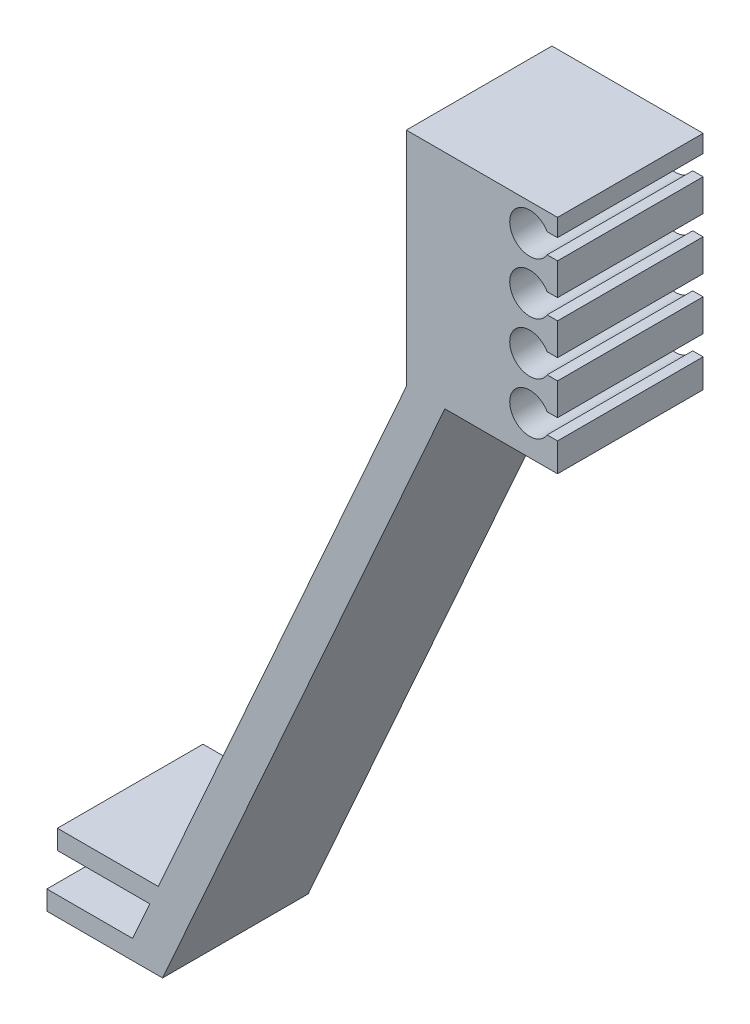
SolidWorks part; units mm, degrees
ref_plane "Front Plane" through (0, 0, 0) normal (0, 0, 1) x (1, 0, 0)
ref_plane "Top Plane" through (0, 0, 0) normal (0, 1, 0) x (1, 0, 0)
ref_plane "Right Plane" through (0, 0, 0) normal (1, 0, 0) x (0, 0, -1)
sketch "Sketch1" plane through (0, 0, 0) normal (0, 0, 1) x (1, 0, 0)
  line L2 (-159.7982, 9.1286) -> (-172.2482, 9.1286)
  line L3 (-172.2482, 9.1286) -> (-172.2482, -9.1594)
  line L7 (-169.2482, -22.8519) -> (-169.2482, 6.1286) construction
  line L13 (-142.8048, 5.144) -> (-142.8048, -5.1748) construction
  line L23 (-159.7982, 6.1286) -> (-159.7982, 9.1286)
  line L28 (-164.5232, 5.1786) -> (-144.5007, 5.1786) construction
  line L30 (-169.2482, 6.1286) -> (-169.2482, 5.1286)
  line L34 (-169.2482, 5.1286) -> (-169.2482, -5.1594)
  line L35 (-172.2482, -0.0154) -> (-169.2482, -0.0154) construction
  line L36 (-169.2482, -6.1594) -> (-169.2482, -5.1594)
  line L37 (-159.7982, -6.1594) -> (-159.7982, -9.1594)
  line L38 (-159.7982, -9.1594) -> (-172.2482, -9.1594)
  arc A5 (-169.2482, 6.1286) -> (-159.7982, 6.1286) centre (-164.5232, 17.404) ccw
  arc A6 (-169.2482, -6.1594) -> (-159.7982, -6.1594) centre (-164.5232, -17.4347) cw
  point P30 (-142.8048, -0.0154)
  dimension "D6" = 12.2253
  dimension "D4" = 3
  dimension "D3" = 3
  dimension "D2" = 1
  dimension "D1" = 18.288
  dimension "D5" = 12.45
extrude "MainBody" add sketch "Sketch1" along normal mid plane 11.9888
sketch "Sketch3" plane through (0, -9.1594, 0) normal (0, -1, 0) x (1, 0, 0)
  line L0 (-159.7982, -5.9944) -> (-162.3382, -6.9944)
  line L1 (-162.3382, -6.9944) -> (-162.3382, -5.9944)
  line L2 (-172.2482, -5.9944) -> (-159.7982, -5.9944) construction
  line L3 (-162.3382, -5.9944) -> (-159.7982, -5.9944)
  line L5 (23.1247, 0) -> (-23.1247, 0) construction
  line L6 (-162.3382, 5.9944) -> (-159.7982, 5.9944)
  line L7 (-162.3382, 6.9944) -> (-162.3382, 5.9944)
  line L8 (-159.7982, 5.9944) -> (-162.3382, 6.9944)
  dimension "D1" = 2.54
  dimension "D2" = 1
extrude "Hook" [suppressed] add sketch "Sketch3" against normal up to vertex up to point (-159.7982, -6.1594, -5.9944)
fillet "Fillet2" [suppressed] radius 1
sketch "Sketch5" [suppressed] plane through (-172.2482, 0, 0) normal (-1, 0, 0) x (0, 0, 1)
  line L1 (-6, 9.1594) -> (6, 9.1594)
  line L2 (-6, 9.1594) -> (-6, -9.1594)
  line L3 (-6, -9.1594) -> (6, -9.1594)
  line L4 (6, 9.1594) -> (6, -9.1594)
extrude "Boss-Extrude1" [suppressed] add sketch "Sketch5" along normal blind 15
sketch "Sketch6" [suppressed] plane through (0, 9.1594, 0) normal (0, 1, 0) x (1, 0, 0)
  line L0 (-187.2482, -6) -> (-187.2482, 6) construction
  circle A0 centre (-182.2482, 0) radius 3.302
  dimension "D1" = 6.604
  dimension "D2" = 5
extrude "Cut-Extrude2" [suppressed] cut sketch "Sketch6" against normal through all
sketch "Sketch7" plane through (-172.2482, 0, 0) normal (-1, 0, 0) x (0, 0, 1)
  circle A0 centre (0, 0) radius 38.1
  dimension "D1" = 76.2
extrude "Boss-Extrude2" [suppressed] add sketch "Sketch7" along normal blind 5
fillet "Fillet3" [suppressed] radius 1
sketch "Sketch8" plane through (0, 0, 5.9944) normal (0, 0, 1) x (1, 0, 0)
  line L6 (-172.2482, -0.635) -> (-173.4343, -0.635)
  line L8 (-172.2482, 0.635) -> (-173.4343, 0.635)
  line L10 (-172.2482, 0.635) -> (-173.4343, 0.635)
  line L11 (-172.2482, 0.635) -> (-172.2482, -0.635)
  line L12 (-159.7982, -9.1594) -> (-159.7982, -6.1594)
  line L14 (-169.2482, -6.1594) -> (-169.2482, 6.1286)
  line L15 (-159.7982, 6.1286) -> (-159.7982, 9.1286)
  line L16 (-159.7982, 9.1286) -> (-172.2482, 9.1286)
  line L17 (-172.2482, 9.1286) -> (-172.2482, -9.1594)
  line L18 (-172.2482, -9.1594) -> (-159.7982, -9.1594)
  line L21 (-169.2482, -6.1594) -> (-169.2482, 6.1286)
  line L22 (-159.7982, 6.1286) -> (-159.7982, 9.1286)
  line L23 (-159.7982, 9.1286) -> (-172.2482, 9.1286)
  line L24 (-172.2482, 9.1286) -> (-172.2482, -9.1594)
  line L25 (-172.2482, -9.1594) -> (-159.7982, -9.1594)
  line L26 (-172.2482, -0.635) -> (-173.4343, -0.635)
  line L33 (-159.7982, -9.1594) -> (-159.7982, -6.1594)
  arc A0 (-173.4343, 0.635) -> (-173.4343, -0.635) centre (-174.5342, 0) ccw
  arc A4 (-159.7982, -6.1594) -> (-169.2482, -6.1594) centre (-164.5232, -17.4347) ccw
  arc A7 (-169.2482, 6.1286) -> (-159.7982, 6.1286) centre (-164.5232, 17.404) ccw
  arc A8 (-159.7982, -6.1594) -> (-169.2482, -6.1594) centre (-164.5232, -17.4347) ccw
  arc A11 (-169.2482, 6.1286) -> (-159.7982, 6.1286) centre (-164.5232, 17.404) ccw
  point P6 (-172.2482, -0.0154)
  dimension "D2" = 1.27
  dimension "D1" = 0
  dimension "D3" = 2.286
extrude "Slot" [suppressed] add sketch "Sketch8" against normal up to surface (12 mm away) up to face at (-165.2732, -0.0154, -5.9944)
sketch "Sketch10" plane through (0, 0, -5.9944) normal (0, 0, -1) x (-1, 0, 0)
  line L0 (166.0232, -9.1594) -> (172.2482, -9.1594)
  line L3 (172.2482, -9.1594) -> (166.0232, -9.1594)
  line L5 (172.2482, -9.1594) -> (187.9767, -44.4861)
  line L6 (195.4932, -61.3685) -> (192.3182, -61.3685)
  line L7 (159.7982, -6.1594) -> (159.7982, -9.1594)
  line L9 (159.7982, -9.1594) -> (172.2482, -9.1594)
  line L10 (172.2482, -9.1594) -> (172.2482, 9.1286)
  line L11 (172.2482, 9.1286) -> (159.7982, 9.1286)
  line L12 (159.7982, 9.1286) -> (159.7982, 6.1286)
  line L13 (169.2482, 6.1286) -> (169.2482, -6.1594)
  line L16 (159.7982, -9.1594) -> (172.2482, -9.1594)
  line L17 (172.2482, -9.1594) -> (172.2482, 9.1286)
  line L18 (172.2482, 9.1286) -> (159.7982, 9.1286)
  line L19 (159.7982, 9.1286) -> (159.7982, 6.1286)
  line L20 (169.2482, 6.1286) -> (169.2482, -6.1594)
  line L21 (195.4932, -61.3685) -> (201.8432, -61.3685)
  line L22 (201.8432, -61.3685) -> (201.8432, -59.781)
  line L24 (192.666, -55.0185) -> (200.9772, -55.0185)
  line L25 (169.0732, -9.1594) -> (192.3182, -61.3685)
  line L28 (201.8432, -59.781) -> (194.7864, -59.781)
  line L31 (193.3728, -56.606) -> (200.9772, -56.606)
  line L42 (200.9772, -55.0185) -> (200.9772, -56.606)
  line L43 (187.9767, -44.4861) -> (195.4932, -61.3685)
  line L49 (159.7982, -6.1594) -> (159.7982, -9.1594)
  arc A4 (169.2482, -6.1594) -> (159.7982, -6.1594) centre (164.5232, -17.4347) ccw
  arc A5 (159.7982, 6.1286) -> (169.2482, 6.1286) centre (164.5232, 17.404) ccw
  arc A8 (169.2482, -6.1594) -> (159.7982, -6.1594) centre (164.5232, -17.4347) ccw
  arc A9 (159.7982, 6.1286) -> (169.2482, 6.1286) centre (164.5232, 17.404) ccw
  dimension "D5" = 6.35
  dimension "D7" = 3.175
  dimension "D8" = 3.175
  dimension "D2" = 57.15
  dimension "D10" = 1.5875
  dimension "D13" = 114
  dimension "D14" = 114
  dimension "D3" = 1.5875
  dimension "D4" = 3.175
extrude "Boss-Extrude3" add sketch "Sketch10" against normal up to surface (11.9888 mm away) contours L6 L5 | L28 L43 L21 L22 | L43 | L43 | L43 | L43 L31 region at (-182.2832, -35.2639, -5.9944) region at (-198.4884, -60.5608, -5.9944) region at (-196.9956, -55.8005, -5.9944) up to face at (-165.2732, -0.0154, 5.9944)
sketch "Sketch11" plane through (0, 0, -5.9944) normal (0, 0, -1) x (-1, 0, 0)
  line L0 (159.7982, -9.1594) -> (159.7982, 9.1286)
  line L11 (169.2482, 6.1286) -> (169.2482, -6.1594)
  line L12 (159.7982, -6.1594) -> (159.7982, -9.1594)
  line L13 (159.7982, -9.1594) -> (169.0732, -9.1594)
  line L14 (169.0732, -9.1594) -> (192.3182, -61.3685)
  line L15 (192.3182, -61.3685) -> (201.8432, -61.3685)
  line L16 (201.8432, -61.3685) -> (201.8432, -59.781)
  line L17 (201.8432, -59.781) -> (194.7864, -59.781)
  line L18 (194.7864, -59.781) -> (193.3728, -56.606)
  line L19 (172.2482, -9.1594) -> (172.2482, 9.1286)
  line L20 (172.2482, 9.1286) -> (159.7982, 9.1286)
  line L21 (159.7982, 9.1286) -> (159.7982, 6.1286)
  line L22 (169.2482, 6.1286) -> (169.2482, -6.1594)
  line L23 (159.7982, -6.1594) -> (159.7982, -9.1594)
  line L24 (159.7982, -9.1594) -> (169.0732, -9.1594)
  line L25 (169.0732, -9.1594) -> (192.3182, -61.3685)
  line L26 (192.3182, -61.3685) -> (201.8432, -61.3685)
  line L27 (201.8432, -61.3685) -> (201.8432, -59.781)
  line L28 (201.8432, -59.781) -> (194.7864, -59.781)
  line L29 (194.7864, -59.781) -> (193.3728, -56.606)
  line L30 (172.2482, -9.1594) -> (172.2482, 9.1286)
  line L31 (172.2482, 9.1286) -> (159.7982, 9.1286)
  line L32 (159.7982, 9.1286) -> (159.7982, 6.1286)
  line L37 (193.3728, -56.606) -> (200.9772, -56.606)
  line L38 (193.3728, -56.606) -> (200.9772, -56.606)
  line L39 (200.9772, -56.606) -> (200.9772, -55.0185)
  line L40 (200.9772, -56.606) -> (200.9772, -55.0185)
  line L41 (192.666, -55.0185) -> (172.2482, -9.1594)
  line L42 (192.666, -55.0185) -> (172.2482, -9.1594)
  line L44 (200.9772, -55.0185) -> (192.666, -55.0185)
  line L45 (200.9772, -55.0185) -> (192.666, -55.0185)
  arc A2 (159.7982, 6.1286) -> (169.2482, 6.1286) centre (164.5232, 17.404) ccw
  arc A3 (169.2482, -6.1594) -> (159.7982, -6.1594) centre (164.5232, -17.4347) ccw
  arc A4 (159.7982, 6.1286) -> (169.2482, 6.1286) centre (164.5232, 17.404) ccw
  arc A5 (169.2482, -6.1594) -> (159.7982, -6.1594) centre (164.5232, -17.4347) ccw
  dimension "D1" = 0
extrude "Boss-Extrude4" add sketch "Sketch11" against normal up to surface (11.9888 mm away) contours L0 region at (-164.5232, -0.0154, -5.9944) up to face at (-180.5907, -27.9312, 5.9944)
sketch "Sketch12" plane through (0, 0, -5.9944) normal (0, 0, -1) x (-1, 0, 0)
  line L0 (159.7982, -9.1594) -> (159.7982, -5.9844)
  line L1 (159.7982, -5.9844) -> (162.0842, -5.9844)
  line L3 (162.0842, -5.1589) -> (159.7982, -5.1589)
  line L4 (162.0842, -5.1589) -> (162.0842, -6.8099)
  line L5 (162.0842, -6.8099) -> (159.7982, -6.8099)
  line L6 (159.7982, -5.1589) -> (159.7982, -6.8099)
  line L7 (162.0842, -5.1589) -> (159.7982, -6.8099) construction
  line L8 (162.0842, -6.8099) -> (159.7982, -5.1589) construction
  line L9 (172.2482, 9.1286) -> (159.7982, 9.1286)
  line L10 (159.7982, 9.1286) -> (159.7982, -9.1594)
  line L11 (159.7982, -9.1594) -> (169.0732, -9.1594)
  line L12 (169.0732, -9.1594) -> (192.3182, -61.3685)
  line L13 (192.3182, -61.3685) -> (201.8432, -61.3685)
  line L14 (201.8432, -61.3685) -> (201.8432, -59.781)
  line L15 (201.8432, -59.781) -> (194.7864, -59.781)
  line L16 (194.7864, -59.781) -> (193.3728, -56.606)
  line L17 (172.2482, -9.1594) -> (172.2482, 9.1286)
  line L18 (172.2482, 9.1286) -> (159.7982, 9.1286)
  line L19 (159.7982, 9.1286) -> (159.7982, -9.1594)
  line L20 (159.7982, -9.1594) -> (169.0732, -9.1594)
  line L21 (169.0732, -9.1594) -> (192.3182, -61.3685)
  line L22 (192.3182, -61.3685) -> (201.8432, -61.3685)
  line L23 (201.8432, -61.3685) -> (201.8432, -59.781)
  line L24 (201.8432, -59.781) -> (194.7864, -59.781)
  line L25 (194.7864, -59.781) -> (193.3728, -56.606)
  line L26 (172.2482, -9.1594) -> (172.2482, 9.1286)
  line L38 (193.3728, -56.606) -> (200.9772, -56.606)
  line L39 (193.3728, -56.606) -> (200.9772, -56.606)
  line L40 (200.9772, -56.606) -> (200.9772, -55.0185)
  line L42 (192.666, -55.0185) -> (172.2482, -9.1594)
  line L43 (192.666, -55.0185) -> (172.2482, -9.1594)
  line L45 (200.9772, -56.606) -> (200.9772, -55.0185)
  line L46 (200.9772, -55.0185) -> (192.666, -55.0185)
  line L47 (200.9772, -55.0185) -> (192.666, -55.0185)
  circle A0 centre (162.0842, -5.9844) radius 1.651
  point P8 (160.9412, -5.9844)
  line M13 (159.7982, 9.1286) -> (159.7982, -9.1594)
  dimension "D4" = 3.302
  dimension "D2" = 3.175
  dimension "D3" = 2.286
  dimension "D5" = 1.651
extrude "Cut-Extrude3" cut sketch "Sketch12" against normal up to surface (11.9888 mm away) contours L5 A0 L3 L4 | L1 A0 L5 L4 | A0 L1 L5 M13 | L3 A0 L1 L4 | A0 L3 L1 M13 region at (-160.1545, -6.4183, -5.9944) region at (-160.1545, -5.5504, -5.9944) region at (-161.2931, -6.3876, -5.9944) region at (-162.4305, -5.9844, -5.9944) region at (-161.2931, -5.5811, -5.9944) up to face at (-185.5346, -36.5207, 5.9944)
pattern_linear "LPattern1" count 4 spacing 4.28 along (0, 1, 0) of "Cut-Extrude3"
sketch "Sketch15" [suppressed] plane through (0, 0, 5.9944) normal (0, 0, 1) x (1, 0, 0)
  line L1 (-172.2482, -9.1594) -> (-179.8682, -9.1594)
  line L2 (-172.2482, -9.1594) -> (-172.2482, 47.9906)
  line L3 (-172.2482, 47.9906) -> (-179.8682, 47.9906)
  line L4 (-179.8682, -9.1594) -> (-179.8682, 47.9906)
  dimension "D1" = 7.62
  dimension "D2" = 69.85
extrude "Boss-Extrude6" [suppressed] add sketch "Sketch15" against normal up to surface (11.9888 mm away) up to face at (-171.9963, -16.131, -5.9944)
sketch "Sketch16" [suppressed] plane through (0, 0, 5.9944) normal (0, 0, 1) x (1, 0, 0)
  line L0 (-172.2482, 9.1286) -> (-172.2482, 47.9906) construction
  line L1 (-172.2482, 44.8156) -> (-174.5342, 44.8156)
  line L2 (-172.2482, 44.8156) -> (-172.2482, 43.1646)
  line L3 (-172.2482, 43.1646) -> (-174.5342, 43.1646)
  line L4 (-174.5342, 44.8156) -> (-174.5342, 43.1646)
  line L5 (-172.2482, 47.9906) -> (-179.8682, 47.9906) construction
  circle A0 centre (-174.5342, 43.9901) radius 1.5875
  line M12 (-172.2482, 9.1286) -> (-172.2482, 47.9906)
  dimension "D4" = 3.175
  dimension "D1" = 3.175
  dimension "D2" = 1.651
  dimension "D3" = 2.286
extrude "Cut-Extrude6" [suppressed] cut sketch "Sketch16" against normal up to surface (11.9888 mm away) contours A0 L3 L1 M12 | L3 A0 L1 L4 | L1 A0 L3 L4 up to face at (-171.9963, -16.131, -5.9944)
pattern_linear "LPattern3" [suppressed] count 9 spacing 5.08 of bodies 124
fillet "Fillet5" [suppressed] radius 2.54
sketch "Sketch17" [suppressed] plane through (0, 9.1286, 0) normal (0, 1, 0) x (1, 0, 0)
  line L1 (-164.7532, 6.096) -> (-167.2932, 6.096)
  line L2 (-164.7532, 6.096) -> (-164.7532, 3.556)
  line L3 (-164.7532, 3.556) -> (-167.2932, 3.556)
  line L4 (-159.7982, 6.096) -> (-172.2482, 6.096)
  line L5 (-172.2482, 6.096) -> (-172.2482, -6.096)
  line L6 (-172.2482, -6.096) -> (-159.7982, -6.096)
  line L7 (-159.7982, -6.096) -> (-159.7982, 6.096)
  line L8 (-159.7982, 6.096) -> (-172.2482, 6.096)
  line L9 (-172.2482, 6.096) -> (-172.2482, -6.096)
  line L10 (-172.2482, -6.096) -> (-159.7982, -6.096)
  line L11 (-159.7982, -6.096) -> (-159.7982, 6.096)
  line L12 (-167.2932, 6.096) -> (-167.2932, 3.556)
  point P8 (-166.0232, 6.096)
  point P9 (-166.0232, 6.096)
  dimension "D2" = 2.54
  dimension "D3" = 2.54
  dimension "D1" = 0
extrude "Boss-Extrude7" [suppressed] add sketch "Sketch17" along normal blind 6.35
pattern_linear "LPattern5" [suppressed] count 9 spacing 24.638 of bodies 126
sketch "Sketch21" [suppressed] plane through (0, 9.1286, 0) normal (0, 1, 0) x (1, 0, 0)
  line L1 (-167.2932, 5.9944) -> (-164.7532, 5.9944)
  line L2 (-167.2932, 5.9944) -> (-167.2932, 3.4544)
  line L3 (-167.2932, 3.4544) -> (-164.7532, 3.4544)
  line L4 (-159.7982, 5.9944) -> (-172.2482, 5.9944)
  line L5 (-172.2482, 5.9944) -> (-172.2482, -5.9944)
  line L6 (-172.2482, -5.9944) -> (-159.7982, -5.9944)
  line L7 (-159.7982, -5.9944) -> (-159.7982, 5.9944)
  line L8 (-159.7982, 5.9944) -> (-172.2482, 5.9944)
  line L9 (-172.2482, 5.9944) -> (-172.2482, -5.9944)
  line L10 (-172.2482, -5.9944) -> (-159.7982, -5.9944)
  line L11 (-159.7982, -5.9944) -> (-159.7982, 5.9944)
  line L12 (-164.7532, 5.9944) -> (-164.7532, 3.4544)
  point P8 (-166.0232, 5.9944)
  point P9 (-166.0232, 5.9944)
  dimension "D2" = 2.54
  dimension "D3" = 2.54
  dimension "D1" = 0
extrude "Boss-Extrude10" [suppressed] add sketch "Sketch21" along normal blind 6.35
sketch "Sketch22" [suppressed] plane through (-172.2482, 0, 0) normal (-1, 0, 0) x (0, 0, 1)
  line L1 (-5.9944, -1.2854) -> (-3.4544, -1.2854)
  line L2 (-5.9944, -1.2854) -> (-5.9944, 1.2546)
  line L3 (-5.9944, 1.2546) -> (-3.4544, 1.2546)
  line L4 (-5.9944, 9.1286) -> (-5.9944, -9.1594)
  line L5 (-5.9944, -9.1594) -> (5.9944, -9.1594)
  line L6 (5.9944, -9.1594) -> (5.9944, 9.1286)
  line L7 (5.9944, 9.1286) -> (-5.9944, 9.1286)
  line L8 (-5.9944, 9.1286) -> (-5.9944, -9.1594)
  line L9 (-5.9944, -9.1594) -> (5.9944, -9.1594)
  line L10 (5.9944, -9.1594) -> (5.9944, 9.1286)
  line L11 (5.9944, 9.1286) -> (-5.9944, 9.1286)
  line L12 (-3.4544, -1.2854) -> (-3.4544, 1.2546)
  point P8 (-5.9944, -0.0154)
  point P9 (-5.9944, -0.0154)
  dimension "D2" = 2.54
  dimension "D3" = 2.54
  dimension "D1" = 0
extrude "Boss-Extrude11" [suppressed] add sketch "Sketch22" along normal blind 6.35
pattern_linear "LPattern6" [suppressed] count 8 spacing 24.638 of bodies 164 160
sketch "Sketch20" [suppressed] plane through (-172.2482, 0, 0) normal (-1, 0, 0) x (0, 0, 1)
  line L1 (-6.096, -1.2854) -> (-3.556, -1.2854)
  line L2 (-6.096, -1.2854) -> (-6.096, 1.2546)
  line L3 (-6.096, 1.2546) -> (-3.556, 1.2546)
  line L4 (-6.096, 9.1286) -> (-6.096, -9.1594)
  line L5 (-6.096, -9.1594) -> (6.096, -9.1594)
  line L6 (6.096, -9.1594) -> (6.096, 9.1286)
  line L7 (6.096, 9.1286) -> (-6.096, 9.1286)
  line L8 (-6.096, 9.1286) -> (-6.096, -9.1594)
  line L9 (-6.096, -9.1594) -> (6.096, -9.1594)
  line L10 (6.096, -9.1594) -> (6.096, 9.1286)
  line L11 (6.096, 9.1286) -> (-6.096, 9.1286)
  line L12 (-3.556, -1.2854) -> (-3.556, 1.2546)
  point P8 (-6.096, -0.0154)
  point P9 (-6.096, -0.0154)
  dimension "D2" = 2.54
  dimension "D3" = 2.54
  dimension "D1" = 0
extrude "Boss-Extrude9" [suppressed] add sketch "Sketch20" along normal blind 6.35
sketch "Sketch23" [suppressed] plane through (0, 9.1286, 0) normal (0, 1, 0) x (1, 0, 0)
  line L0 (-167.2932, -5.9944) -> (-164.7532, -5.9944)
  line L4 (-159.7982, 5.9944) -> (-172.2482, 5.9944)
  line L5 (-172.2482, 5.9944) -> (-172.2482, -5.9944)
  line L6 (-172.2482, -5.9944) -> (-159.7982, -5.9944)
  line L7 (-159.7982, -5.9944) -> (-159.7982, 5.9944)
  line L8 (-159.7982, 5.9944) -> (-172.2482, 5.9944)
  line L9 (-172.2482, 5.9944) -> (-172.2482, -5.9944)
  line L10 (-172.2482, -5.9944) -> (-159.7982, -5.9944)
  line L11 (-159.7982, -5.9944) -> (-159.7982, 5.9944)
  line L13 (-164.7532, -5.9944) -> (-167.2932, -5.9944)
  line L14 (-164.7532, -5.9944) -> (-164.7532, -3.4544)
  line L15 (-164.7532, -3.4544) -> (-167.2932, -3.4544)
  line L16 (-167.2932, -5.9944) -> (-167.2932, -3.4544)
  point P8 (-166.0232, -5.9944)
  point P9 (-166.0232, -5.9944)
  dimension "D2" = 2.54
  dimension "D3" = 2.54
  dimension "D1" = 0
extrude "Boss-Extrude12" [suppressed] add sketch "Sketch23" along normal blind 6.35
sketch "Sketch27" [suppressed] plane through (-172.2482, 0, 0) normal (-1, 0, 0) x (0, 0, 1)
  line L1 (5.9944, -1.2854) -> (3.4544, -1.2854)
  line L2 (5.9944, -1.2854) -> (5.9944, 1.2546)
  line L3 (5.9944, 1.2546) -> (3.4544, 1.2546)
  line L4 (-5.9944, 9.1286) -> (-5.9944, -9.1594)
  line L5 (-5.9944, -9.1594) -> (5.9944, -9.1594)
  line L6 (5.9944, -9.1594) -> (5.9944, 9.1286)
  line L7 (5.9944, 9.1286) -> (-5.9944, 9.1286)
  line L8 (-5.9944, 9.1286) -> (-5.9944, -9.1594)
  line L9 (-5.9944, -9.1594) -> (5.9944, -9.1594)
  line L10 (5.9944, -9.1594) -> (5.9944, 9.1286)
  line L11 (5.9944, 9.1286) -> (-5.9944, 9.1286)
  line L12 (3.4544, -1.2854) -> (3.4544, 1.2546)
  point P8 (5.9944, -0.0154)
  point P9 (5.9944, -0.0154)
  dimension "D2" = 2.54
  dimension "D3" = 2.54
  dimension "D1" = 0
extrude "Boss-Extrude16" [suppressed] add sketch "Sketch27" along normal blind 6.35
pattern_linear "LPattern7" [suppressed] count 8 spacing 24.638 of bodies 180 165
sketch "Sketch25" [suppressed] plane through (-172.2482, 0, 0) normal (-1, 0, 0) x (0, 0, 1)
  line L1 (5.9944, 1.2546) -> (3.4544, 1.2546)
  line L2 (5.9944, 1.2546) -> (5.9944, -1.2854)
  line L3 (5.9944, -1.2854) -> (3.4544, -1.2854)
  line L4 (-5.9944, 9.1286) -> (-5.9944, -9.1594)
  line L5 (-5.9944, -9.1594) -> (5.9944, -9.1594)
  line L6 (5.9944, -9.1594) -> (5.9944, 9.1286)
  line L7 (5.9944, 9.1286) -> (-5.9944, 9.1286)
  line L8 (-5.9944, 9.1286) -> (-5.9944, -9.1594)
  line L9 (-5.9944, -9.1594) -> (5.9944, -9.1594)
  line L10 (5.9944, -9.1594) -> (5.9944, 9.1286)
  line L11 (5.9944, 9.1286) -> (-5.9944, 9.1286)
  line L12 (3.4544, 1.2546) -> (3.4544, -1.2854)
  point P8 (5.9944, -0.0154)
  point P9 (5.9944, -0.0154)
  dimension "D2" = 2.54
  dimension "D3" = 2.54
  dimension "D1" = 0
extrude "Boss-Extrude14" [suppressed] add sketch "Sketch25" along normal blind 6.35
sketch "Sketch26" [suppressed] plane through (-172.2482, 0, 0) normal (-1, 0, 0) x (0, 0, 1)
  line L1 (-5.9944, 1.2546) -> (-3.4544, 1.2546)
  line L2 (-5.9944, 1.2546) -> (-5.9944, -1.2854)
  line L3 (-5.9944, -1.2854) -> (-3.4544, -1.2854)
  line L4 (-5.9944, 9.1286) -> (-5.9944, -9.1594)
  line L5 (-5.9944, -9.1594) -> (5.9944, -9.1594)
  line L6 (5.9944, -9.1594) -> (5.9944, 9.1286)
  line L7 (5.9944, 9.1286) -> (-5.9944, 9.1286)
  line L8 (-5.9944, 9.1286) -> (-5.9944, -9.1594)
  line L9 (-5.9944, -9.1594) -> (5.9944, -9.1594)
  line L10 (5.9944, -9.1594) -> (5.9944, 9.1286)
  line L11 (5.9944, 9.1286) -> (-5.9944, 9.1286)
  line L12 (-3.4544, 1.2546) -> (-3.4544, -1.2854)
  point P8 (-5.9944, -0.0154)
  point P9 (-5.9944, -0.0154)
  dimension "D2" = 2.54
  dimension "D3" = 2.54
  dimension "D1" = 0
extrude "Boss-Extrude15" [suppressed] add sketch "Sketch26" along normal blind 6.35
sketch "Sketch28" [suppressed] plane through (0, -9.1594, 0) normal (0, -1, 0) x (1, 0, 0)
  line L1 (-167.2932, 5.9944) -> (-164.7532, 5.9944)
  line L2 (-167.2932, 5.9944) -> (-167.2932, 3.4544)
  line L3 (-167.2932, 3.4544) -> (-164.7532, 3.4544)
  line L4 (-172.2482, -5.9944) -> (-159.7982, -5.9944)
  line L5 (-159.7982, -5.9944) -> (-159.7982, 5.9944)
  line L6 (-159.7982, 5.9944) -> (-172.2482, 5.9944)
  line L7 (-172.2482, 5.9944) -> (-172.2482, -5.9944)
  line L8 (-172.2482, -5.9944) -> (-159.7982, -5.9944)
  line L9 (-159.7982, -5.9944) -> (-159.7982, 5.9944)
  line L10 (-159.7982, 5.9944) -> (-172.2482, 5.9944)
  line L11 (-172.2482, 5.9944) -> (-172.2482, -5.9944)
  line L12 (-164.7532, 5.9944) -> (-164.7532, 3.4544)
  point P8 (-166.0232, 5.9944)
  point P9 (-166.0232, 5.9944)
  line M11 (-159.7982, 5.9944) -> (-172.2482, 5.9944)
  dimension "D2" = 2.54
  dimension "D3" = 2.54
  dimension "D1" = 0
extrude "Boss-Extrude17" [suppressed] add sketch "Sketch28" along normal blind 6.35 contours L12 L2 L3 M11
sketch "Sketch29" [suppressed] plane through (0, 9.1286, 0) normal (0, 1, 0) x (1, 0, 0)
  line L1 (-167.2932, -5.9944) -> (-164.7532, -5.9944)
  line L2 (-167.2932, -5.9944) -> (-167.2932, -3.4544)
  line L3 (-167.2932, -3.4544) -> (-164.7532, -3.4544)
  line L4 (-159.7982, 5.9944) -> (-172.2482, 5.9944)
  line L5 (-172.2482, 5.9944) -> (-172.2482, -5.9944)
  line L6 (-172.2482, -5.9944) -> (-159.7982, -5.9944)
  line L7 (-159.7982, -5.9944) -> (-159.7982, 5.9944)
  line L8 (-159.7982, 5.9944) -> (-172.2482, 5.9944)
  line L9 (-172.2482, 5.9944) -> (-172.2482, -5.9944)
  line L10 (-172.2482, -5.9944) -> (-159.7982, -5.9944)
  line L11 (-159.7982, -5.9944) -> (-159.7982, 5.9944)
  line L12 (-164.7532, -5.9944) -> (-164.7532, -3.4544)
  point P8 (-166.0232, -5.9944)
  point P9 (-166.0232, -5.9944)
  line M7 (-172.2482, -5.9944) -> (-159.7982, -5.9944)
  dimension "D2" = 2.54
  dimension "D3" = 2.54
  dimension "D1" = 0
extrude "Boss-Extrude18" [suppressed] add sketch "Sketch29" along normal blind 6.35 contours L12 L3 L2 M7
equation "\"HookThickness\"= 3mm"
equation "\"D3@Sketch1\"=\"HookThickness\""
equation "\"D4@Sketch1\"=\"HookThickness\""
equation "\"CylinderDiameter\"=3"
equation "\"D1@Sketch7\"=\"CylinderDiameter\""
equation "\"Mount Tolerance\"= .005in"
equation "\"Mount Thickness\"= .0625in"
equation "\"Mount Angle\"= 114"
equation "\"D14@Sketch10\"=\"Mount Angle\""
equation "\"D13@Sketch10\"= \"Mount Angle\""
equation "\"Joint Radius\"= .05in"
equation "\"Joint Thickness\"= .05in"
equation "\"Joint Tolerance\"= .015in"
equation "\"D5@Sketch12\"= \"Joint Thickness\" + \"Joint Tolerance\""
